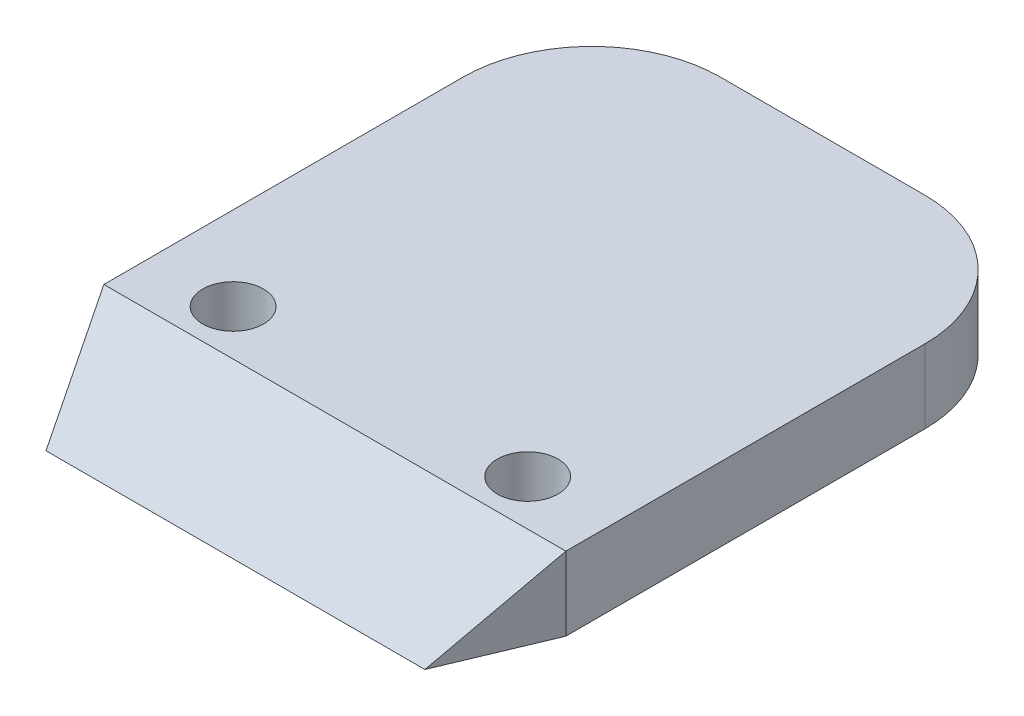
SolidWorks part; units mm, degrees
ref_plane "Front Plane" through (0, 0, 0) normal (0, 0, 1) x (1, 0, 0)
ref_plane "Top Plane" through (0, 0, 0) normal (0, 1, 0) x (1, 0, 0)
ref_plane "Right Plane" through (0, 0, 0) normal (1, 0, 0) x (0, 0, -1)
sketch "Sketch4" plane through (0, 0, 0) normal (0, 0, 1) x (1, 0, 0)
  line L1 (-6.23, -9.975) -> (6.23, -9.975)
  line L2 (-6.23, -9.975) -> (-6.23, 7.275)
  line L3 (-6.23, 7.275) -> (6.23, 7.275)
  line L4 (6.23, -9.975) -> (6.23, 7.275)
  point P4 (0, 7.275)
  dimension "D1" = 12.46
  dimension "D2" = 17.25
  dimension "D3" = 9.975
extrude "Boss-Extrude3" add sketch "Sketch4" along normal blind 6
sketch "Sketch8" plane through (0, -9.975, 0) normal (0, -1, 0) x (-1, 0, 0)
  circle A0 centre (0, -23.55) radius 12.5468
  circle A1 centre (0, -23.55) radius 11.15
  dimension "D1" = 22.3
  dimension "D2" = 23.55
extrude "Boss-Extrude6" add sketch "Sketch8" along normal blind 7.3 and the other way up to surface (17.25 mm away) other way up to face at (0, 7.275, 3)
sketch "Sketch5" plane through (0, 7.275, 0) normal (0, 1, 0) x (1, 0, 0)
  line L8 (12.5468, -23.55) -> (12.5468, 0)
  line L9 (12.5468, 0) -> (6.23, 0)
  line L10 (-12.5468, -23.55) -> (-12.5468, 0)
  line L11 (-12.5468, 0) -> (-6.23, 0)
  line L12 (-6.23, 0) -> (-6.23, -29.7)
  line L14 (6.23, -29.7) -> (6.23, 0)
  line L15 (-6.23, -29.7) -> (6.23, -29.7)
  line L16 (6.23, -6) -> (-6.23, -6) construction
  circle A0 centre (0, -23.55) radius 12.5468 construction
  arc A1 (-12.5468, -23.55) -> (12.5468, -23.55) centre (0, -23.55) ccw
  dimension "D1" = 23.7
  dimension "D2" = 23.55
extrude "Boss-Extrude4" add sketch "Sketch5" against normal up to surface (17.25 mm away) up to face at (0, -9.975, 3)
sketch "Sketch6" plane through (0, 7.275, 0) normal (0, 1, 0) x (1, 0, 0)
  line L0 (6.23, -6) -> (-6.23, -6) construction
  line L3 (6.23, -29.7) -> (-6.23, -29.7) construction
  circle A0 centre (0, -3.5) radius 2
  circle A1 centre (0, -32.2) radius 2
  dimension "D1" = 4
  dimension "D3" = 4
  dimension "D2" = 2.5
  dimension "D4" = 2.5
extrude "Cut-Extrude1" cut sketch "Sketch6" against normal blind 5
chamfer "Chamfer1" distance 0.5 angle 60 2 edges at (0, 7.275, 5.5) (0, 7.275, 34.2) first distance on face at (0, 7.275, 5.5)
sketch "Sketch10" plane through (0, 7.275, 0) normal (0, 1, 0) x (1, 0, 0)
  line L1 (-6.23, -6) -> (6.23, -6)
  line L2 (-6.23, -6) -> (-6.23, -29.7)
  line L3 (-6.23, -29.7) -> (6.23, -29.7)
  line L4 (6.23, -6) -> (6.23, -29.7)
extrude "Cut-Extrude3" cut sketch "Sketch10" against normal up to surface (17.25 mm away) up to face at (0, -9.975, 10.3399)
ref_plane "Plane1" through (0, 0, 36.0968) normal (0, 0, 1) x (1, 0, 0)
sketch "Sketch11" plane through (0, 0, 36.0968) normal (0, 0, 1) x (1, 0, 0)
  line L0 (-11.15, -9.975) -> (11.15, -9.975) construction
  line L1 (-2.5, -6.975) -> (2.5, -6.975)
  line L2 (-2.5, -6.975) -> (-2.5, -9.975)
  line L3 (-2.5, -9.975) -> (2.5, -9.975)
  line L4 (2.5, -6.975) -> (2.5, -9.975)
  point P4 (0, -6.975)
  dimension "D1" = 0
  dimension "D2" = 5
  dimension "D3" = 3
extrude "Cut-Extrude4" cut sketch "Sketch11" against normal up to next
sketch "Sketch13" plane through (0, -17.275, 0) normal (0, -1, 0) x (1, 0, 0)
  line L0 (-12.5468, 23.55) -> (-12.5468, 0)
  line L1 (-12.5468, 0) -> (12.5468, 0)
  line L2 (12.5468, 0) -> (12.5468, 23.55)
  arc A0 (-12.5468, 23.55) -> (12.5468, 23.55) centre (0, 23.55) ccw
  point P3 (0, 0)
extrude "Boss-Extrude7" add sketch "Sketch13" against normal up to surface (7.3 mm away) up to face at (0, -9.975, 10.3399)
sketch "Sketch15" plane through (0, 7.275, 0) normal (0, 1, 0) x (1, 0, 0)
  line L0 (-12.5468, 0) -> (12.5468, 0)
  line L1 (12.5468, 0) -> (12.5468, -23.55)
  line L2 (-12.5468, 0) -> (-12.5468, -23.55)
  line L3 (6.23, -6) -> (6.23, -29.7) construction
  line L4 (-6.23, -0.8) -> (6.23, -0.8)
  line L5 (-6.23, -0.8) -> (-6.23, -33.5)
  line L6 (-5.23, -34.5) -> (5.23, -34.5)
  line L7 (6.23, -0.8) -> (6.23, -33.5)
  arc A0 (-12.5468, -23.55) -> (12.5468, -23.55) centre (0, -23.55) ccw
  circle A1 centre (0, -3.5) radius 2 construction
  arc A2 (5.23, -34.5) -> (6.23, -33.5) centre (5.23, -33.5) ccw
  arc A3 (-6.23, -33.5) -> (-5.23, -34.5) centre (-5.23, -33.5) ccw
  point P15 (0, -0.8)
  dimension "D1" = 0.8
  dimension "D3" = 1
  dimension "D2" = 2.7
  dimension "D4" = 0
  dimension "D5" = 34.5
extrude "Boss-Extrude9" add sketch "Sketch15" along normal blind 10
sketch "Sketch17" plane through (-12.5468, 4.7282, 0) normal (1, 0, 0) x (0, -1, 0)
  line L0 (26.9782, 26.5) -> (26.9782, 0)
  line L1 (26.9782, 0) -> (-17.5218, 0)
  line L2 (-17.5218, 0) -> (-17.5218, 26.5)
  line L3 (-17.5218, 26.5) -> (-13.5218, 26.5)
  line L4 (-13.5218, 26.5) -> (-13.5218, 5)
  line L5 (-13.5218, 5) -> (22.9782, 5)
  line L6 (22.9782, 5) -> (22.9782, 26.5)
  line L7 (22.9782, 26.5) -> (26.9782, 26.5)
  point P2 (4.7282, 5)
  point P10 (4.7282, 0)
  dimension "D1" = 4
  dimension "D2" = 36.5
  dimension "D3" = 0
  dimension "D4" = 26.5
  dimension "D5" = 5
extrude "Boss-Extrude10" add sketch "Sketch17" along normal up to surface (25.0936 mm away) up to face at (12.5468, 0, 11.775)
sketch "Sketch18" plane through (0, -18.25, 0) normal (0, 1, 0) x (0, 0, 1)
  line L0 (-26.5, -12.5468) -> (-26.5, 12.5468) construction
  line L1 (-26.5, 6.2191) -> (-5, 6.2191)
  line L2 (-26.5, 6.2191) -> (-26.5, -6.2191)
  line L3 (-26.5, -6.2191) -> (-5, -6.2191)
  line L4 (-5, 6.2191) -> (-5, -6.2191)
  line L5 (-5, -12.5468) -> (-5, 12.5468) construction
  point P6 (-26.5, 0)
  point P7 (-26.5, 0)
  dimension "D1" = 0
extrude "Cut-Extrude5" cut sketch "Sketch18" against normal blind 2
sketch "Sketch19" plane through (0, -20.25, 0) normal (0, 1, 0) x (0, 0, 1)
  line L0 (-26.5, -12.5468) -> (-26.5, 12.5468) construction
  line L1 (-26.5, 12.5468) -> (-26.5, -12.5468) construction
  circle A0 centre (-20, 0) radius 3.5
  point P7 (-26.5, 0)
  dimension "D1" = 7
  dimension "D2" = 6.5
extrude "Cut-Extrude6" cut sketch "Sketch19" against normal through all both and the other way through all
fillet "Fillet1" radius 7 4 edges at (12.5468, -20.25, -26.5) (-12.5468, -20.25, -26.5) (-12.5468, 20.25, -26.5) (12.5468, 20.25, -26.5)
ref_plane "Plane2" through (0, 0, 0) normal (1, 0, 0) x (0, 0, -1)
ref_plane "Plane3" through (0, 0, 0) normal (0, -1, 0) x (-1, 0, 0)
sketch "Sketch20" plane through (0, 17.275, 0) normal (0, 1, 0) x (1, 0, 0)
  line L1 (12.5468, 0) -> (-12.5468, 0)
  line L2 (12.5468, 0) -> (12.5468, -36.0968)
  line L3 (12.5468, -36.0968) -> (-12.5468, -36.0968)
  line L4 (-12.5468, 0) -> (-12.5468, -36.0968)
extrude "Cut-Extrude7" cut sketch "Sketch20" against normal through all both and the other way through all
sketch "Sketch21" plane through (0, 22.25, 0) normal (0, 1, 0) x (1, 0, 0)
  line L0 (12.5468, 0) -> (-0.0254, -30)
  line L1 (-0.0254, -30) -> (-12.5468, 0)
  line L2 (-12.5468, 0) -> (12.5468, 0)
  dimension "D1" = 30
extrude "Boss-Extrude11" add sketch "Sketch21" against normal up to vertex (44.5 mm away) up to point (-12.5468, -22.25, 0)
sketch "Sketch22" plane through (0, 0, 0) normal (1, 0, 0) x (0, 0, -1)
  line L13 (0, 22.25) -> (-30, 0.01)
  line L14 (-30, -22.25) -> (-30, 22.25) construction
  line L15 (-30, 0.01) -> (-30, 22.25)
  line L16 (-30, 22.25) -> (0, 22.25)
  line L17 (0, -22.25) -> (-30, -22.25)
  line L18 (-30, -22.25) -> (-30, -0.01)
  line L19 (-30, -0.01) -> (0, -22.25)
  dimension "D1" = 0.02
  dimension "D2" = 0.01
extrude "Cut-Extrude8" cut sketch "Sketch22" against normal through all both and the other way through all
sketch "Sketch23" plane through (0, 0, 0) normal (0, 0, -1) x (-1, 0, 0)
  line L0 (12.5468, 18.25) -> (0, 0)
  line L1 (0, 0) -> (12.5468, -22.25)
  line L2 (12.5468, -22.25) -> (12.5468, 18.25)
extrude "Cut-Extrude9" cut sketch "Sketch23" against normal through all
sketch "Sketch24" plane through (0, 22.25, 0) normal (0, 1, 0) x (1, 0, 0)
  circle A0 centre (0, 20) radius 6.5
  dimension "D1" = 13
extrude "Boss-Extrude12" add sketch "Sketch24" against normal blind 5
sketch "Sketch25" plane through (0, 17.25, 0) normal (0, -1, 0) x (1, 0, 0)
  circle A0 centre (0, -20) radius 6.075
  dimension "D1" = 12.15
extrude "Boss-Extrude13" add sketch "Sketch25" along normal blind 5
fillet "Fillet2" radius 1 1 edges at (0, 12.25, -26.075)
sketch "Sketch26" plane through (0, -20.25, 0) normal (0, 1, 0) x (1, 0, 0)
  line L0 (-6.2191, 5) -> (-2.5, 5)
  line L1 (12.5468, 5) -> (-12.5468, 5) construction
  line L2 (-2.5, 5) -> (-3.1585, 20)
  line L4 (3.1585, 20) -> (3.4438, 26.5)
  line L5 (-6.2191, 26.5) -> (-6.2191, 5)
  line L6 (2.5, 5) -> (6.2191, 5)
  line L7 (6.2191, 5) -> (6.2191, 26.5)
  line L8 (3.4438, 26.5) -> (6.2191, 26.5)
  line L10 (3.1585, 20) -> (2.5, 5)
  line L11 (0, -10.725) -> (0, 10.725) construction
  line L13 (-3.1585, 20) -> (-3.4439, 26.5)
  line L14 (-3.4439, 26.5) -> (-6.2191, 26.5)
  line L15 (6.2191, 5) -> (6.2191, 26.4676) construction
  line L16 (5.5468, 26.5) -> (-5.5468, 26.5) construction
  circle A0 centre (0, 20) radius 3.5 construction
  dimension "D1" = 5
  dimension "D2" = 2.5
  dimension "D3" = 0
  dimension "D4" = 0
  dimension "D5" = 6.317
  dimension "D6" = 3.1585
extrude "Boss-Extrude14" add sketch "Sketch26" along normal up to surface (2 mm away) up to face at (-9.7194, -18.25, -14.2975)
sketch "Sketch27" plane through (0, -22.25, 0) normal (0, -1, 0) x (1, 0, 0)
  line L0 (0, -10.725) -> (0, 10.725) construction
  circle A0 centre (0, -10) radius 0.75
  circle A1 centre (0, -20) radius 3.5 construction
  circle A2 centre (0, -7.5) radius 0.75
  circle A3 centre (0, -12.5) radius 0.75
  dimension "D1" = 1.5
  dimension "D4" = 7.5
  dimension "D5" = 12.5
  dimension "D2" = 10
  dimension "D3" = 0
extrude "Cut-Extrude10" cut sketch "Sketch27" against normal up to next
sketch "Sketch28" plane through (12.5468, 0, 0) normal (1, 0, 0) x (0, 0, -1)
  line L0 (5, 18.25) -> (-35.2329, 18.25)
  line L1 (-35.2329, 18.25) -> (-35.2329, -25.6165)
  line L2 (-35.2329, -25.6165) -> (31.5987, -25.6165)
  line L3 (31.5987, -25.6165) -> (31.5987, 10.8921)
  line L4 (31.5987, 10.8921) -> (5, 10.8921)
  line L5 (5, -18.25) -> (5, 18.25) construction
  line L6 (5, 10.8921) -> (5, 18.25)
extrude "Cut-Extrude11" cut sketch "Sketch28" along normal through all both and the other way through all
sketch "Sketch29" plane through (0, 18.25, 0) normal (0, -1, 0) x (1, 0, 0)
  line L0 (0, -2.2) -> (0, 2.2) construction
  line L1 (10.2856, 5.3957) -> (-10.2947, 5.3957) construction
  circle A0 centre (-8, -2.4733) radius 1.65
  circle A1 centre (8, -2.4733) radius 1.65
  dimension "D1" = 3.3
  dimension "D2" = 16
  dimension "D3" = 8
  dimension "D4" = 7.869
extrude "Cut-Extrude12" cut sketch "Sketch29" against normal through all both and the other way through all
sketch "Sketch30" plane through (0, 18.25, 0) normal (0, -1, 0) x (1, 0, 0)
  line L0 (0, -2.2) -> (0, 2.2) construction
  circle A0 centre (0, -2.4733) radius 2.25
  circle A2 centre (-8, -2.4733) radius 1.65 construction
  dimension "D1" = 0
  dimension "D2" = 4.5
extrude "Boss-Extrude15" add sketch "Sketch30" along normal blind 6
fillet "Fillet3" radius 1 1 edges at (0, 12.25, -4.7233)
